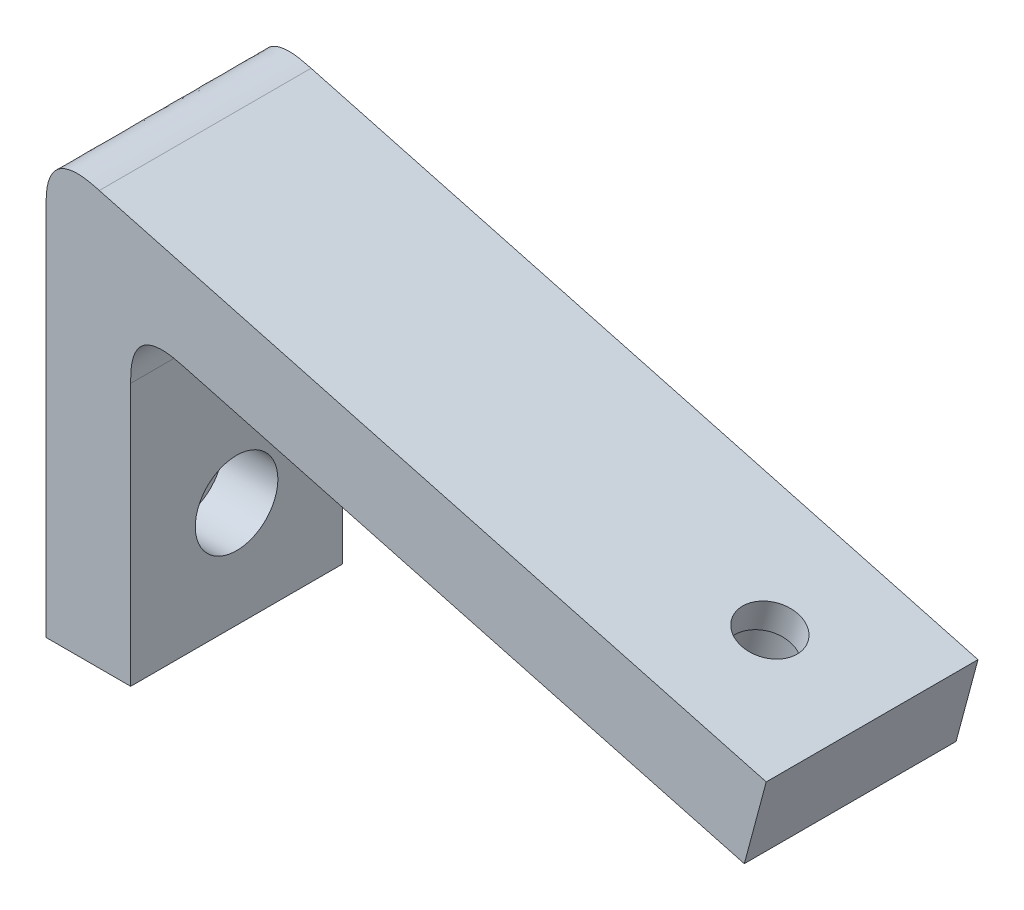
SolidWorks part; units mm, degrees
ref_plane "Front Plane" through (0, 0, 0) normal (0, 0, 1) x (1, 0, 0)
ref_plane "Top Plane" through (0, 0, 0) normal (0, 1, 0) x (1, 0, 0)
ref_plane "Right Plane" through (0, 0, 0) normal (1, 0, 0) x (0, 0, -1)
sketch "Sketch1" plane through (0, 0, 0) normal (0, 0, 1) x (1, 0, 0)
  line L0 (0, 0) -> (0, 51.3408)
  line L1 (0, 51.3408) -> (86.3931, 28.1918)
  line L2 (86.3931, 28.1918) -> (83.7635, 18.378)
  line L3 (83.7635, 18.378) -> (10.16, 38.1)
  line L4 (10.16, 38.1) -> (10.16, 0)
  line L5 (10.16, 0) -> (0, 0)
  dimension "D1" = 38.1
  dimension "D2" = 76.2
  dimension "D3" = 75
  dimension "D4" = 10.16
  dimension "D5" = 10.16
extrude "Boss-Extrude1" add sketch "Sketch1" along normal blind 25.4 contours L5 L4 L3 L2 L1 L0 region at (1.005, 25.6704, 0)
sketch "Sketch2" plane through (0, 0, 0) normal (-1, 0, 0) x (0, 0, 1)
  line L0 (0, 12.7) -> (25.4, 12.7) construction
  line L1 (0, 0) -> (0, 51.3408) construction
  line L2 (25.4, 0) -> (25.4, 51.3408) construction
  line L3 (25.4, 0) -> (0, 0) construction
  point P6 (12.7, 12.7)
  dimension "D1" = 12.7
sketch "Sketch3" plane through (12.8352, 47.9016, 0) normal (0.2588, 0.9659, 0) x (0.9659, -0.2588, 0)
  line L0 (63.4528, 0) -> (63.4528, -25.4) construction
  line L1 (-13.288, 0) -> (76.1528, 0) construction
  line L2 (-13.288, -25.4) -> (76.1528, -25.4) construction
  line L3 (76.1528, -25.4) -> (76.1528, 0) construction
  point P6 (63.4528, -12.7)
  dimension "D1" = 12.7
hole_wizard "1/4 Clearance Hole1" positions "Sketch4" profile "Sketch5" hole size "1/4" standard "ANSI Inch"
sketch "Sketch4" plane through (0, 0, 0) normal (-1, 0, 0) x (0, 0, 1)
  point P0 (12.7, 12.7)
sketch "Sketch5" plane through (0, 12.7, 12.7) normal (0, 1, 0) x (0, 0, 1)
  line L0 (0, 0) -> (0, 12.1898)
  line L1 (0, 12.1898) -> (3.3782, 10.16)
  line L2 (3.3782, 10.16) -> (3.3782, 0)
  line L5 (3.3782, 0) -> (0, 0)
  line L10 (0, 12.1898) -> (-3.3782, 10.16) construction
  line L11 (0, -6.35) -> (0, 107.95) construction
  dimension "Hole Dia." = 6.7564
  dimension "Hole Depth" = 10.16
  dimension "Drill Angle" = 118
hole_wizard "1/4 Clearance Hole2" positions "Sketch6" profile "Sketch7" hole size "1/4" standard "ANSI Inch"
sketch "Sketch6" plane through (12.8352, 47.9016, 0) normal (0.2588, 0.9659, 0) x (0.9659, -0.2588, 0)
  point P0 (63.4528, -12.7)
sketch "Sketch7" plane through (74.1259, 31.4788, 12.7) normal (0, 0, 1) x (-0.9659, 0.2588, 0)
  line L0 (0, 0) -> (0, 12.1898)
  line L1 (0, 12.1898) -> (3.3782, 10.16)
  line L2 (3.3782, 10.16) -> (3.3782, 0)
  line L5 (3.3782, 0) -> (0, 0)
  line L10 (0, 12.1898) -> (-3.3782, 10.16) construction
  line L11 (0, -6.35) -> (0, 107.95) construction
  dimension "Hole Dia." = 6.7564
  dimension "Hole Depth" = 10.16
  dimension "Drill Angle" = 118
fillet "Fillet1" radius 5.08 2 edges at (10.16, 38.1, 12.7) (0, 51.3408, 12.7) curvature continuous yes
sketch "Sketch8" plane through (10.2056, 38.0878, 0) normal (-0.2588, -0.9659, 0) x (0.9659, -0.2588, 0)
  circle A0 centre (63.4528, 12.7) radius 4.953
  dimension "D1" = 9.906
extrude "Cut-Extrude1" cut sketch "Sketch8" against normal blind 6.604
sketch "Sketch9" plane through (10.16, 0, 0) normal (1, 0, 0) x (0, 0, -1)
  line L0 (0, 12.7) -> (-25.4, 12.7) construction
  circle A0 centre (-12.7, 12.7) radius 4.953
  dimension "D1" = 9.906
extrude "Cut-Extrude2" cut sketch "Sketch9" against normal blind 6.604
